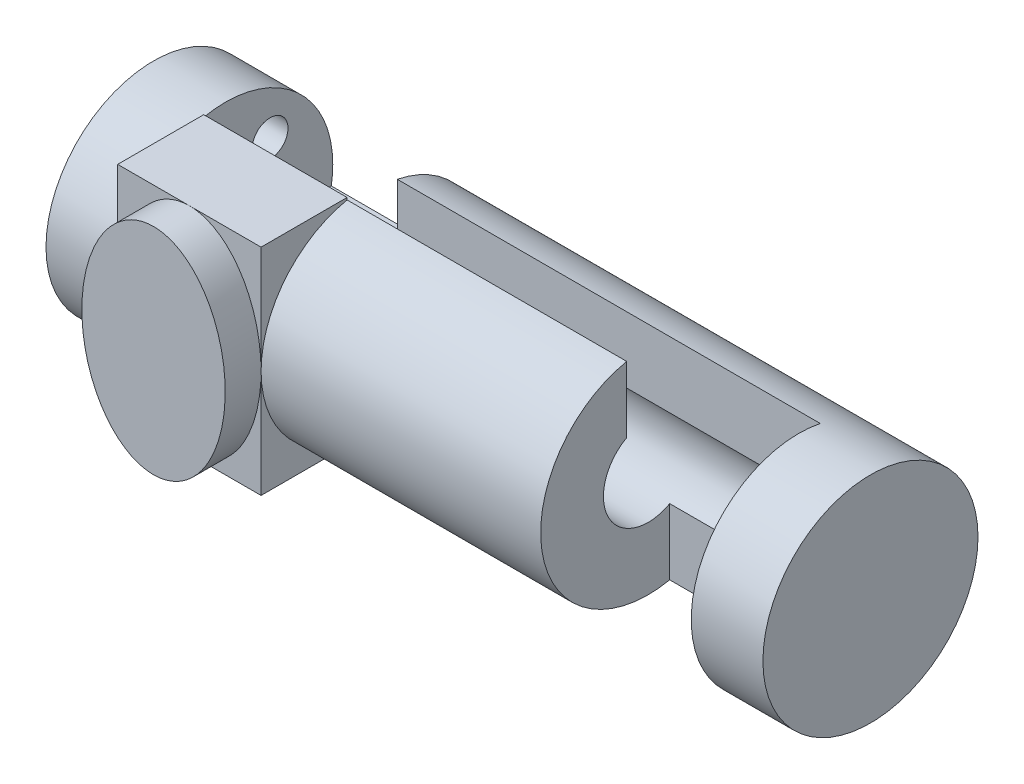
SolidWorks part; units mm, degrees
ref_plane "Front Plane" through (0, 0, 0) normal (0, 0, 1) x (1, 0, 0)
ref_plane "Top Plane" through (0, 0, 0) normal (0, 1, 0) x (1, 0, 0)
ref_plane "Right Plane" through (0, 0, 0) normal (1, 0, 0) x (0, 0, -1)
sketch "Sketch2" plane through (0, 0, 0) normal (1, 0, 0) x (0, 0, -1)
  circle A0 centre (0, 0) radius 30
  dimension "D1" = 60
extrude "Boss-Extrude1" add sketch "Sketch2" along normal blind 200
sketch "Sketch3" plane through (200, 0, 0) normal (1, 0, 0) x (0, 0, -1)
  line L1 (6, -5) -> (6, 29.3939)
  line L2 (6, -5) -> (6, -29.3939)
  circle A0 centre (0, 0) radius 30 construction
  arc A3 (6, 29.3939) -> (6, -29.3939) centre (0, 0) ccw
  dimension "D2" = 6
extrude "Cut-Extrude2" cut sketch "Sketch3" against normal blind 42 from offset 20 offset against normal yes
sketch "Sketch5" plane through (0, 0, 0) normal (-1, 0, 0) x (0, 0, 1)
  line L0 (6, 29.3939) -> (6, -5)
  line L1 (6, -5) -> (-29.5804, -5)
  circle A0 centre (0, 0) radius 30 construction
  arc A3 (-29.5804, -5) -> (6, 29.3939) centre (0, 0) cw
  dimension "D1" = 5
  dimension "D2" = 6
extrude "Cut-Extrude8" cut sketch "Sketch5" against normal blind 42 from offset 20 offset against normal yes
sketch "Sketch32" plane through (0, 0, 0) normal (-1, 0, 0) x (0, 0, 1)
  line L5 (10.922, -30) -> (30, -30)
  line L6 (30, -30) -> (30, 30)
  line L7 (30, 30) -> (0, 30)
  line L8 (0, -30) -> (10.922, -30)
  line L9 (0, 30) -> (6.4653, -29.295)
  arc A0 (0, -30) -> (6.4653, -29.295) centre (0, 0) ccw
  circle A1 centre (0, 0) radius 30 construction
  circle A2 centre (0, 0) radius 30 construction
  point P13 (30, 0)
  dimension "D1" = 60
extrude "Boss-Extrude4" add sketch "Sketch32" against normal blind 40 from offset 20 offset against normal yes
sketch "Sketch33" plane through (0, 0, 30) normal (0, 0, 1) x (1, 0, 0)
  line L0 (60, 30) -> (20, 30) construction
  line L1 (20, -30) -> (20, 0) construction
  ellipse E0 centre (40, 0) end of major axis (40, 30) minor radius 20
  dimension "D1" = 30
  dimension "D2" = 20
extrude "Boss-Extrude7" add sketch "Sketch33" along normal blind 10
sketch "Sketch4" plane through (200, 0, 0) normal (1, 0, 0) x (0, 0, -1)
  line L0 (6, 29.3939) -> (6, -5)
  line L1 (6, -5) -> (-6, -5)
  line L2 (-6, -5) -> (-6, 29.3939)
  line L3 (-6, 29.3939) -> (-6, 31.4841)
  line L4 (-6, 31.4841) -> (6, 31.4841)
  line L5 (6, 31.4841) -> (6, 29.3939)
  circle A0 centre (0, 0) radius 30 construction
  dimension "D1" = 12
  dimension "D2" = 5
extrude "Cut-Extrude3" cut sketch "Sketch4" against normal blind 160 from offset 20 offset against normal yes
sketch "Sketch34" plane through (0, 0, 0) normal (-1, 0, 0) x (0, 0, 1)
  circle A0 centre (0, 0) radius 12.5
  dimension "D1" = 25
extrude "Cut-Extrude9" cut sketch "Sketch34" against normal blind 160 from offset 20 offset against normal yes
sketch "Sketch35" plane through (0, 0, 0) normal (-1, 0, 0) x (0, 0, 1)
  circle A0 centre (0, 0) radius 30 construction
  circle A1 centre (-12.5, 15) radius 5
  dimension "D1" = 12.5
  dimension "D3" = 10
  dimension "D2" = 15
extrude "Cut-Extrude10" cut sketch "Sketch35" against normal blind 80
thread "Thread2" pitch 1.5 method extrude profile "Thread Profile2" start angle 0, offset 0, length 10, pitch 1.5, diameter 10
ref_plane "Plane2" through (80, 15, -7.5) normal (0, -1, 0) x (0, 0, 1)
sketch "Thread Profile2" plane through (80, 15, -7.5) normal (0, -1, 0) x (0, 0, 1)
  line L0 (0, 0) -> (0, 1.5) construction
  line L11 (0, 0) -> (0, 1.3125)
  line L12 (0, 1.3125) -> (-0.8119, 0.8437)
  line L13 (-0.8119, 0.8437) -> (-0.8119, 0.4687)
  line L15 (-0.8119, 0.4687) -> (0, 0)
  line L17 (-0.8119, 0.6562) -> (0, 0.6562) construction
  point P2 (0, 0)
  dimension "Pitch" = 1.5
  dimension "Profile_Angle" = 60
  dimension "Profile_Land" = 0.375
  dimension "Profile_Height" = 0.8119
sketch "Sketch42" plane through (138, 0, 0) normal (1, 0, 0) x (0, 0, -1)
  point P0 (-25, 0)
sketch "Sketch43" plane through (0, 0, 40) normal (0, 0, 1) x (1, 0, 0)
  ellipse E0 centre (40, 0) end of major axis (40, 30) minor radius 20 construction
  point P0 (40, 30)
  point P16 (20, 0)
sketch "Sketch45" plane through (138, 0, 0) normal (1, 0, 0) x (0, 0, -1)
  arc A2 (0, 12.5) -> (0, -12.5) centre (0, 0) ccw
  point P4 (0, 0)
  point P7 (0, 0)
  point P8 (0, 12.5)
sketch "Sketch47" plane through (20, 0, 0) normal (1, 0, 0) x (0, 0, -1)
  arc A1 (12.5, 0) -> (0, 12.5) centre (0, 0) ccw
  point P4 (0, 0)
  point P5 (0, -12.5)
  point P6 (0, 0)
  dimension "D1" = 12.5
sketch3d "3DSketch1"
  line L0 (20, 12.5, 0) -> (138, 12.5, 0)
